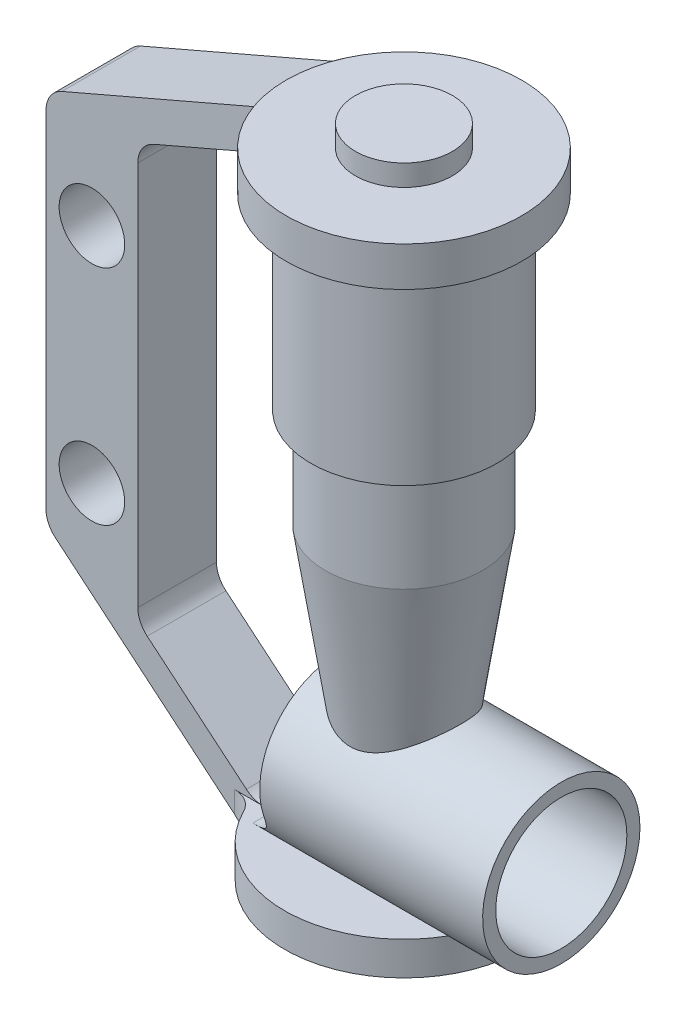
SolidWorks part; units mm, degrees
ref_plane "Front Plane" through (0, 0, 0) normal (0, 0, 1) x (1, 0, 0)
ref_plane "Top Plane" through (0, 0, 0) normal (0, 1, 0) x (1, 0, 0)
ref_plane "Right Plane" through (0, 0, 0) normal (1, 0, 0) x (0, 0, -1)
sketch "Sketch2" plane through (0, 0, 0) normal (0, 0, 1) x (1, 0, 0)
  line L0 (0, 47.4815) -> (0, -202.5185) construction
  line L1 (0, 47.4815) -> (18.4843, 47.4815)
  line L2 (18.4843, 47.4815) -> (18.4843, 39.3946)
  line L3 (18.4843, 39.3946) -> (44.8721, 39.3946)
  line L4 (44.8721, 39.3946) -> (44.8721, 24.3464)
  line L5 (44.8721, 24.3464) -> (35.4459, 24.3464)
  line L6 (35.4459, 24.3464) -> (35.4459, -47.075)
  line L7 (35.4459, -47.075) -> (30.0077, -47.075)
  line L8 (30.0077, -47.075) -> (30.0077, -85.1422)
  line L9 (30.0077, -85.1422) -> (18.5463, -160.9367)
  line L10 (18.5463, -160.9367) -> (18.5463, -189.741)
  line L11 (18.5463, -189.741) -> (45.5176, -189.741)
  line L12 (45.5176, -189.741) -> (45.5176, -202.5185)
  line L13 (45.5176, -202.5185) -> (0, -202.5185)
  line L14 (0, 47.4815) -> (0, -202.5185)
  point P7 (0, 0)
  point P15 (44.8721, 24.3464)
  point P16 (37.6212, -47.075)
  point P17 (0, 0)
  point P18 (30.0077, -85.1422)
  dimension "D1" = 250
revolve "Revolve1" add sketch "Sketch2" angle 360 about L0
sketch "Sketch3" plane through (0, 0, 0) normal (0, 0, 1) x (1, 0, 0)
  line L0 (-42.2853, 24.3464) -> (-86.4744, 5.2797)
  line L1 (-86.4744, 5.2797) -> (-86.4744, -152.7902)
  line L2 (-86.4744, -152.7902) -> (-42.2853, -189.741)
  line L3 (-42.2853, -189.741) -> (-42.2853, -202.5185)
  line L4 (-42.2853, -202.5185) -> (-44.0807, -202.5185)
  line L5 (-44.0807, -202.5185) -> (-121.4744, -137.8022)
  line L6 (-121.4744, -137.8022) -> (-121.4744, 5.2261)
  line L7 (-121.4744, 5.2261) -> (-42.2853, 39.3946)
  line L8 (-45.5176, -202.5185) -> (45.5176, -202.5185) construction
  line L9 (-42.2853, 24.3464) -> (-42.2853, 39.3946)
  line L10 (45.5176, -189.741) -> (-45.5176, -189.741) construction
  line L11 (44.8721, 39.3946) -> (-44.8721, 39.3946) construction
  line L12 (-44.8721, 24.3464) -> (44.8721, 24.3464) construction
  line L13 (-103.9744, -30.8053) -> (-103.9744, -115.8053) construction
  circle A0 centre (-103.9744, -30.8053) radius 12.5
  circle A1 centre (-103.9744, -115.8053) radius 12.5
  point P11 (-81.1902, -31.2945)
  point P14 (-109.7037, -97.6013)
  point P17 (-110.5433, 3.7055)
  point P18 (-99.9321, -65.8053)
  point P19 (-121.4744, -137.8022)
  dimension "D2" = 25
  dimension "D4" = 25
  dimension "D1" = 35
  dimension "D3" = 17.5
  dimension "D5" = 85
extrude "Boss-Extrude1" add sketch "Sketch3" along normal blind 15 and the other way blind 15
sketch "Sketch4" plane through (0, 0, 0) normal (1, 0, 0) x (0, 0, -1)
  line L0 (0, 0) -> (0, -170) construction
  circle A0 centre (0, -170) radius 25
  circle A1 centre (0, -170) radius 30
  dimension "D1" = 50
  dimension "D2" = 60
  dimension "D3" = 170
extrude "Boss-Extrude2" add sketch "Sketch4" along normal blind 60
sketch "Sketch5" plane through (0, 0, 0) normal (1, 0, 0) x (0, 0, -1)
  line L0 (0, 0) -> (0, -170) construction
  circle A0 centre (0, -170) radius 30
  dimension "D2" = 60
  dimension "D1" = 170
extrude "Boss-Extrude3" add sketch "Sketch5" along normal blind 5 and the other way blind 25
fillet "Fillet1" radius 10 8 edges at (-42.975, -196.1297, 15) (-42.975, -196.1297, -15) (-121.4744, -137.8022, 0) (-121.4744, 5.2261, 0) (-86.4744, 5.2797, 0) (-86.4744, -152.7902, 0) (-42.2853, -189.741, 0) (-25, -189.741, 0)
sketch "Sketch6" plane through (60, 0, 0) normal (1, 0, 0) x (0, 0, -1)
  circle A0 centre (0, -170) radius 25
  dimension "D2" = 50
  dimension "D1" = 170
extrude "Cut-Extrude1" cut sketch "Sketch6" against normal blind 65
